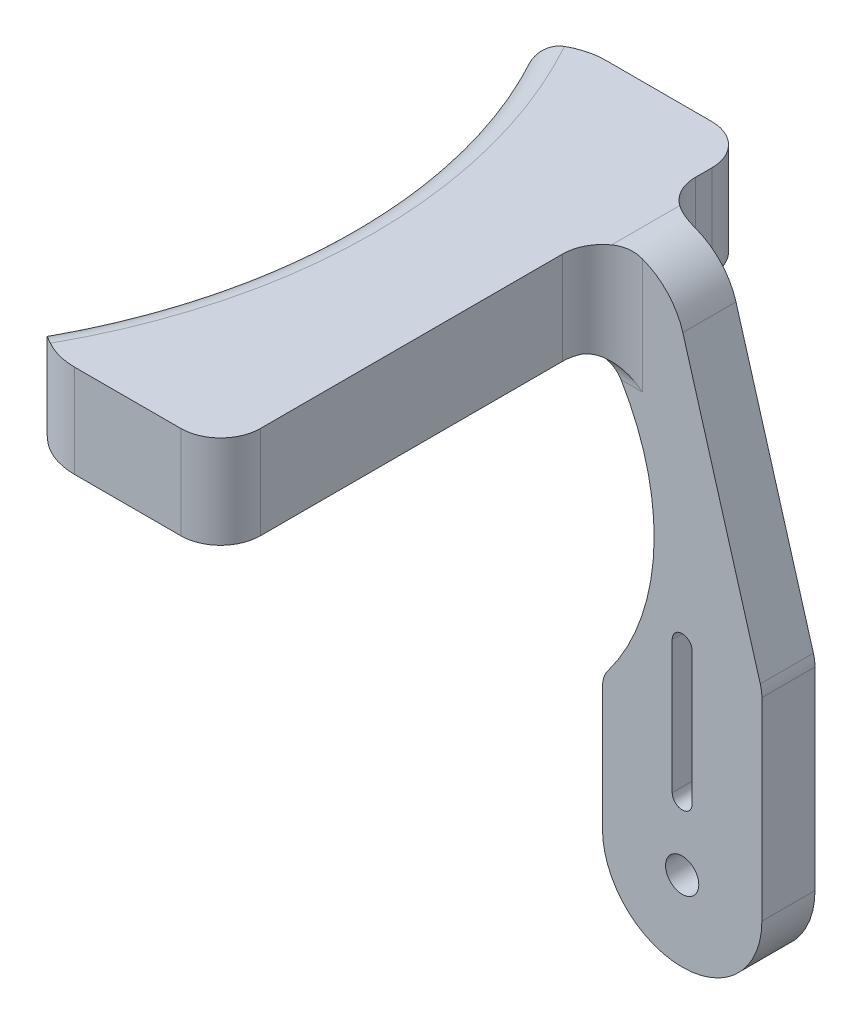
SolidWorks part; units mm, degrees
ref_plane "Alzado" through (0, 0, 0) normal (0, 0, 1) x (1, 0, 0)
ref_plane "Planta" through (0, 0, 0) normal (0, 1, 0) x (1, 0, 0)
ref_plane "Vista lateral" through (0, 0, 0) normal (1, 0, 0) x (0, 0, -1)
sketch "Croquis1" plane through (0, 0, 0) normal (0, 0, 1) x (1, 0, 0)
  line L0 (-6, 0) -> (-6, 39)
  line L1 (6, 0) -> (6, 15)
  line L3 (-6, 39) -> (-1, 39)
  line L4 (-1, 39) -> (6, 15)
  arc A0 (-6, 0) -> (6, 0) centre (0, 0) ccw
  dimension "D1" = 6
  dimension "D2" = 39
  dimension "D3" = 15
  dimension "D4" = 5
extrude "Saliente-Extruir1" add sketch "Croquis1" along normal blind 4
sketch "Croquis3" plane through (0, 39, 0) normal (0, 1, 0) x (1, 0, 0)
  line L0 (-6, -32.75) -> (-6, 7.25)
  line L1 (-6, 7.25) -> (-21, 7.25)
  line L2 (-21, 7.25) -> (-21, 5.25)
  line L3 (-21, -30.75) -> (-21, -32.75)
  line L4 (-21, -32.75) -> (-6, -32.75)
  line L6 (-6, -12.75) -> (-54.4664, -12.75) construction
  line L7 (-6, -4) -> (-6, 0) construction
  line L8 (-1, -4) -> (-6, -4) construction
  arc A0 (-21, -30.75) -> (-21, 5.25) centre (-54.4664, -12.75) ccw
  dimension "D3" = 38
  dimension "D1" = 15
  dimension "D2" = 40
  dimension "D4" = 8.75
  dimension "D5" = 2
extrude "Saliente-Extruir2" add sketch "Croquis3" against normal blind 7
fillet "Redondeo1" radius 3 5 edges at (6, 15, 2) (-6, 35.5, -7.25) (-6, 35.5, 32.75) (-6, 35.5, 4) (-6, 35.5, 0)
fillet "Redondeo2" radius 5 3 edges at (-21, 35.5, 32.75) (-21, 35.5, -7.25) (-1, 39, 2)
sketch "Croquis4" plane through (0, 0, 0) normal (0, 0, -1) x (-1, 0, 0)
  line L0 (0, 15) -> (0, 5) construction
  line L1 (0.75, 15) -> (0.75, 5)
  line L2 (-0.75, 15) -> (-0.75, 5)
  circle A0 centre (0, 0) radius 1.25
  arc A1 (0.75, 15) -> (-0.75, 15) centre (0, 15) ccw
  arc A2 (-0.75, 5) -> (0.75, 5) centre (0, 5) ccw
  point P5 (0, 10)
  dimension "D1" = 2.5
  dimension "D2" = 0.75
  dimension "D3" = 5
  dimension "D4" = 10
extrude "Cortar-Extruir1" cut sketch "Croquis4" against normal blind 10
fillet "Redondeo3" radius 2 2 edges at (-16.4664, 32, 12.75) (-16.4664, 39, 12.75)
sketch "Croquis6" plane through (0, 0, 4) normal (0, 0, 1) x (1, 0, 0)
  line L0 (-6, 32) -> (-6, 0) construction
  line L1 (-6, 0) -> (-6, 10) construction
  line L2 (-6, 32) -> (-6, 10)
  arc A0 (-6, 32) -> (-6, 10) centre (-19.6107, 21) cw
  arc A1 (-6, 0) -> (6, 0) centre (0, 0) ccw construction
  dimension "D2" = 17.5
  dimension "D1" = 10
extrude "Cortar-Extruir2" cut sketch "Croquis6" against normal blind 10
fillet "Redondeo4" radius 2 2 edges at (-6, 32, 2) (-6, 10, 2)
fillet "Redondeo5" radius 2 2 edges at (-4.9956, 32, 0) (-4.9956, 32, 4)
